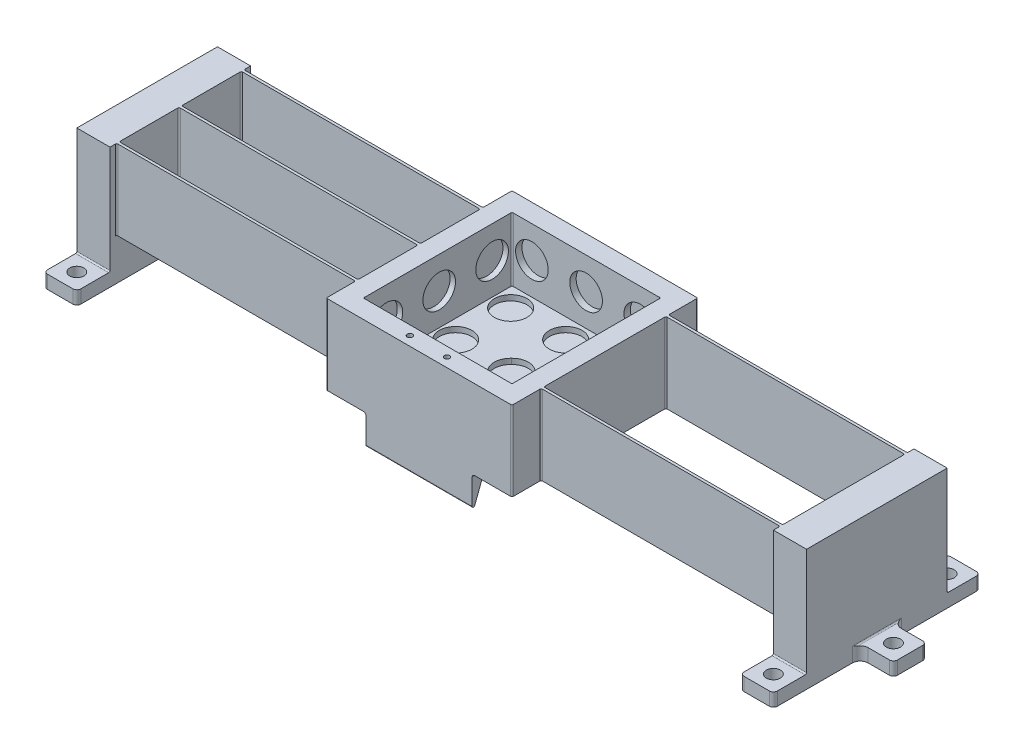
SolidWorks part; units mm, degrees
ref_plane "Front Plane" through (0, 0, 0) normal (0, 0, 1) x (1, 0, 0)
ref_plane "Top Plane" through (0, 0, 0) normal (0, 1, 0) x (1, 0, 0)
ref_plane "Right Plane" through (0, 0, 0) normal (1, 0, 0) x (0, 0, -1)
sketch "Sketch1" plane through (0, 0, 0) normal (0, 1, 0) x (1, 0, 0)
  line L1 (-35, -35) -> (35, -35)
  line L2 (-35, -35) -> (-35, 35)
  line L3 (-35, 35) -> (35, 35)
  line L4 (35, -35) -> (35, 35)
  line L5 (-35, -35) -> (35, 35) construction
  line L6 (-35, 35) -> (35, -35) construction
  point P0 (0, 0)
  dimension "D1" = 70
  dimension "D2" = 70
extrude "Boss-Extrude1" add sketch "Sketch1" along normal blind 30
shell "Shell1" thickness 7 removed face at (0, 30, 0)
sketch "Sketch2" plane through (0, 30, 0) normal (0, 1, 0) x (1, 0, 0)
  line L0 (-35, 35) -> (-35, -35) construction
  line L1 (-28, -28) -> (28, -28) construction
  line L2 (-28, -28) -> (-28, 28) construction
  line L3 (-28, 28) -> (28, 28) construction
  line L4 (28, -28) -> (28, 28) construction
  line L5 (-28, -28) -> (28, 28) construction
  line L6 (-28, 28) -> (28, -28) construction
  line L7 (35, 35) -> (-35, 35) construction
  point P0 (0, 0)
  dimension "D1" = 7
  dimension "D2" = 7
sketch "Sketch3" plane through (35, 0, 0) normal (1, 0, 0) x (0, 0, -1)
  line L0 (-35, 30) -> (35, 30) construction
  line L1 (-24, 30) -> (-23, 30)
  line L2 (-24, 30) -> (-24, 0)
  line L3 (-24, 0) -> (-23, 0)
  line L4 (-23, 30) -> (-23, 0)
  line L5 (-35, 0) -> (35, 0) construction
  line L6 (-28, 30) -> (28, 30) construction
  line L7 (-0.5, 30) -> (0.5, 30)
  line L8 (-0.5, 30) -> (-0.5, 0)
  line L9 (-0.5, 0) -> (0.5, 0)
  line L10 (0.5, 30) -> (0.5, 0)
  line L11 (28, 30) -> (-28, 30) construction
  line L12 (24, 30) -> (23, 30)
  line L13 (24, 30) -> (24, 0)
  line L14 (24, 0) -> (23, 0)
  line L15 (23, 30) -> (23, 0)
  line L16 (-23.5, 30) -> (-23.5, 0) construction
  line L17 (0, 30) -> (0, 0) construction
  line L18 (23.5, 0) -> (23.5, 30) construction
  dimension "D1" = 23
  dimension "D2" = 23
  dimension "D3" = 1
extrude "Boss-Extrude2" add sketch "Sketch3" along normal blind 90
sketch "Sketch5" plane through (125, 0, 0) normal (1, 0, 0) x (0, 0, -1)
  line L0 (-24, 30) -> (-24, 0) construction
  line L1 (-26.5, 30) -> (26.5, 30)
  line L2 (-26.5, 30) -> (-26.5, 0)
  line L3 (-26.5, 0) -> (26.5, 0)
  line L4 (26.5, 30) -> (26.5, 0)
  line L5 (28, 30) -> (-28, 30) construction
  line L6 (24, 0) -> (35, 0) construction
  line L7 (24, 0) -> (24, 30) construction
  dimension "D1" = 2.5
  dimension "D2" = 2.5
extrude "Boss-Extrude3" add sketch "Sketch5" along normal blind 12.5
sketch "Sketch6" plane through (0, 0, 0) normal (0, -1, 0) x (1, 0, 0)
  line L1 (125, 26.5) -> (137.5, 26.5)
  line L2 (125, 26.5) -> (125, -26.5)
  line L3 (125, -26.5) -> (137.5, -26.5)
  line L4 (137.5, 26.5) -> (137.5, -26.5)
extrude "Boss-Extrude4" add sketch "Sketch6" along normal blind 15.75
sketch "Sketch8" plane through (0, -15.75, 0) normal (0, -1, 0) x (1, 0, 0)
  line L1 (137.5, -26.5) -> (125, -26.5)
  line L2 (137.5, -26.5) -> (137.5, -39)
  line L3 (137.5, -39) -> (125, -39)
  line L4 (125, -26.5) -> (125, -39)
  line L5 (137.5, 26.5) -> (125, 26.5)
  line L6 (137.5, 26.5) -> (137.5, 39)
  line L7 (137.5, 39) -> (125, 39)
  line L8 (125, 26.5) -> (125, 39)
  line L13 (137.5, -26.5) -> (137.5, 26.5) construction
  line L14 (150, -6.25) -> (137.5, -6.25)
  line L15 (150, -6.25) -> (150, 6.25)
  line L16 (150, 6.25) -> (137.5, 6.25)
  line L17 (137.5, -6.25) -> (137.5, 6.25)
  line L18 (150, -6.25) -> (137.5, 6.25) construction
  line L19 (150, 6.25) -> (137.5, -6.25) construction
  line L20 (125, 0) -> (150, 0) construction
  line L21 (125, 0.5) -> (125, -0.5) construction
  point P13 (143.75, 0)
  point P19 (137.5, 0)
  point P20 (137.5, 0)
extrude "Boss-Extrude5" add sketch "Sketch8" against normal blind 5
hole_wizard "Ø5.0mm Dowel Hole1" positions "Sketch9" profile "Sketch10" hole size "Ø5.0" standard "ANSI Metric"
sketch "Sketch9" plane through (0, -10.75, 0) normal (0, 1, 0) x (1, 0, 0)
  line L0 (131.25, 39) -> (131.25, 32.75) construction
  line L1 (125, 39) -> (137.5, 39) construction
  line L2 (131.25, 32.75) -> (137.5, 32.75) construction
  line L3 (137.5, 39) -> (137.5, 26.5) construction
  line L5 (137.5, 0) -> (143.75, 0) construction
  line L6 (137.5, -6.25) -> (137.5, 6.25) construction
  line L7 (143.75, 0) -> (143.75, 6.25) construction
  line L8 (137.5, 6.25) -> (150, 6.25) construction
  line L10 (131.25, -26.5) -> (131.25, -32.75) construction
  line L11 (125, -26.5) -> (137.5, -26.5) construction
  line L12 (131.25, -32.75) -> (137.5, -32.75) construction
  line L13 (137.5, -26.5) -> (137.5, -39) construction
  point P0 (131.25, 32.75)
  point P2 (143.75, 0)
  point P4 (131.25, -32.75)
sketch "Sketch10" plane through (131.25, -10.75, -32.75) normal (1, 0, 0) x (0, 0, 1)
  line L0 (0, 0) -> (0, 18.1023)
  line L1 (0, 18.1023) -> (2.65, 16.51)
  line L2 (2.65, 16.51) -> (2.65, 0)
  line L5 (2.65, 0) -> (0, 0)
  line L10 (0, 18.1023) -> (-2.65, 16.51) construction
  line L11 (0, -6.35) -> (0, 107.95) construction
  dimension "Hole Dia." = 5.3
  dimension "Hole Depth" = 16.51
  dimension "Drill Angle" = 118
mirror "Mirror1" about plane through (0, 0, 0) normal (1, 0, 0) of "Boss-Extrude2", "Boss-Extrude3", "Boss-Extrude5", "Boss-Extrude4", "Ø5.0mm Dowel Hole1"
fillet "Fillet2" radius 1.5 12 edges at (150, -13.25, 6.25) (150, -13.25, -6.25) (137.5, -13.25, -39) (125, -13.25, -39) (137.5, -13.25, 39) (125, -13.25, 39) (-125, -13.25, -39) (-137.5, -13.25, -39) (-150, -13.25, -6.25) (-150, -13.25, 6.25) (-125, -13.25, 39) (-137.5, -13.25, 39)
sketch "Sketch11" plane through (0, 6, 0) normal (0, 1, 0) x (1, 0, 0)
  line L26 (-28, -28) -> (-28, 28) construction
  line L32 (-28, -28) -> (28, -28) construction
  circle A0 centre (-21, -21) radius 6.15
  dimension "D1" = 12.3
  dimension "D2" = 0.85
  dimension "D3" = 0.85
extrude "Cut-Extrude1" cut sketch "Sketch11" against normal blind 2.05
pattern_linear "LPattern1" count 3 spacing 20.75 along (1, 0, 0) count 3 spacing 20.75 along (0, 0, -1) of "Cut-Extrude1"
sketch "Sketch14" plane through (0, 6, 0) normal (0, 1, 0) x (1, 0, 0)
  line L0 (-28, 0) -> (0, 0) construction
  line L1 (-28, 28) -> (-28, -28) construction
  line L2 (0, 0) -> (0, -28) construction
  line L3 (-28, -28) -> (28, -28) construction
  circle A0 centre (0, 0) radius 6.15
  dimension "D1" = 12.3
extrude "Cut-Extrude4" cut sketch "Sketch14" against normal blind 2.05
sketch "Sketch12" plane through (-28, 0, 0) normal (1, 0, 0) x (0, 0, -1)
  line L5 (-28, 18) -> (-19.35, 18) construction
  line L6 (-28, 30) -> (-28, 6) construction
  circle A0 centre (-19.35, 18) radius 6.15
  dimension "D1" = 12.3
  dimension "D2" = 2.5
extrude "Cut-Extrude2" cut sketch "Sketch12" against normal blind 2.05
pattern_linear "LPattern2" count 3 spacing 19.925 along (0, 0, -1) of "Cut-Extrude2"
sketch "Sketch13" plane through (0, 0, -28) normal (0, 0, -1) x (-1, 0, 0)
  line L6 (-28, 30) -> (-28, 6) construction
  line L7 (-20.35, 18) -> (-28, 18) construction
  circle A0 centre (-20.35, 18) radius 6.15
  dimension "D1" = 12.3
  dimension "D3" = 1.5
extrude "Cut-Extrude3" cut sketch "Sketch13" along normal blind 2.4
pattern_linear "LPattern3" count 3 spacing 20.425 along (-1, 0, 0) of "Cut-Extrude3"
mirror "Mirror2" about plane through (0, 0, 0) normal (1, 0, 0) of "LPattern2", "Cut-Extrude2"
sketch "Sketch24" plane through (0, 30, 0) normal (0, 1, 0) x (1, 0, 0)
  line L1 (35, 0.5) -> (125, 0.5)
  line L2 (35, 0.5) -> (35, -0.5)
  line L3 (35, -0.5) -> (125, -0.5)
  line L4 (125, 0.5) -> (125, -0.5)
extrude "Cut-Extrude6" cut sketch "Sketch24" against normal through all both and the other way through all
fillet "Fillet4" radius 0.5 4 edges at (-35, 15, 35) (35, 15, 35) (-35, 15, -35) (35, 15, -35)
sketch "Sketch19" plane through (0, 0, 0) normal (1, 0, 0) x (0, 0, -1)
  line L0 (-30, 0) -> (-35, -13.25)
  line L1 (-35, -13.25) -> (-35, 0)
  line L2 (-35, 0) -> (-30, 0)
  line L3 (0, 0) -> (-30, 0) construction
  line L4 (37.5, -15.75) -> (-37.5, -15.75) construction
  dimension "D1" = 5
  dimension "D2" = 30
  dimension "D3" = 2.5
extrude "Boss-Extrude8" add sketch "Sketch19" along normal mid plane 40
sketch "Sketch20" plane through (0, 0, 0) normal (1, 0, 0) x (0, 0, -1)
  line L0 (-35, 20) -> (-42.5, 20)
  line L1 (-42.5, 20) -> (-42.5, 30)
  line L2 (-26.5, 30) -> (-42.5, 30) construction
  line L5 (-42.5, 30) -> (-40, 30)
  line L6 (-40, 30) -> (-40, 22.5)
  line L7 (-40, 22.5) -> (-35, 22.5)
  line L8 (-35, 22.5) -> (-35, 20)
  line L9 (-35, 30) -> (-35, 0) construction
  line L10 (-35, 0) -> (-35, 30) construction
  dimension "D1" = 5
  dimension "D2" = 10
  dimension "D3" = 2.5
  dimension "D4" = 2.5
extrude "Place For Sensor" [suppressed] add sketch "Sketch20" along normal mid plane 10
fillet "Place For Sensor Fillet5" [suppressed] radius 0.5
fillet "Place For Sensor Fillet6" [suppressed] radius 1.5
hole_wizard "Place For Sensor Ø3.0mm Dowel Hole2" [suppressed] positions "Sketch21" profile "Sketch22" hole size "Ø3.0" standard "ANSI Metric"
sketch "Sketch21" [suppressed] plane through (0, 0, 32.5) normal (0, 0, 1) x (1, 0, 0)
  line L0 (-2.5, 27.5) -> (2.5, 27.5) construction
  line L2 (-18, 30) -> (18, 30) construction
  line L3 (-5, 28.5) -> (-5, 20.5) construction
  line L4 (5, 28.5) -> (5, 20.5) construction
  point P0 (-2.5, 27.5)
  point P2 (2.5, 27.5)
  dimension "D1" = 2.5
  dimension "D2" = 2.5
  dimension "D3" = 2.5
sketch "Sketch22" plane through (-2.5, 27.5, 32.5) normal (1, 0, 0) x (0, -1, 0)
  line L0 (0, 0) -> (0, 2.5)
  line L1 (0, 2.5) -> (1.65, 2.5)
  line L2 (1.65, 2.5) -> (1.65, 0)
  line L5 (1.65, 0) -> (0, 0)
  line L11 (0, -6.35) -> (0, 107.95) construction
  dimension "Thru Hole Dia." = 3.3
  dimension "Thru Hole Depth" = 2.5
sketch "Sketch23" plane through (0, 30, 0) normal (0, 1, 0) x (1, 0, 0)
  line L1 (-28, -28) -> (28, -28) construction
  circle A0 centre (-7, -31.5) radius 1
  circle A1 centre (7, -31.5) radius 1
  dimension "D4" = 2
  dimension "D1" = 3.5
  dimension "D2" = 14
  dimension "D3" = 7
extrude "Cut-Extrude5" cut sketch "Sketch23" against normal blind 6
fillet "Fillet3" radius 0.5 4 edges at (28, 18, -28) (-28, 18, -28) (28, 18, 28) (-28, 18, 28)
fillet "Fillet1" radius 0.5 26 edges at (125, 15, 23) (125, 15, 24) (125, 15, -23) (125, 15, -24) (35, 15, 24) (35, 15, 23) (35, 15, -24) (35, 15, -23) (-125, 15, 24) (-125, 15, 23) (-125, 15, 0.5) (-125, 15, -0.5) (-125, 15, -24) (-125, 15, -23) (-35, 15, 24) (-35, 15, 23) (-35, 15, 0.5) (-35, 15, -0.5) (-35, 15, -23) (-35, 15, -24) (-131.25, -10.75, -26.5) (-137.5, -10.75, 0) (-131.25, -10.75, 26.5) (131.25, -10.75, 26.5) (131.25, -10.75, -26.5) (137.5, -10.75, 0)
fillet "Fillet5" radius 0.5 1 edges at (0, -13.25, 35)
fillet "Fillet6" radius 1 3 edges at (-20, 0, 32.5) (20, 0, 32.5) (0, 0, 30)
fillet "Fillet8" radius 3 4 edges at (137.5, -13, 6.25) (137.5, -13, -6.25) (-137.5, -13, -6.25) (-137.5, -13, 6.25)
